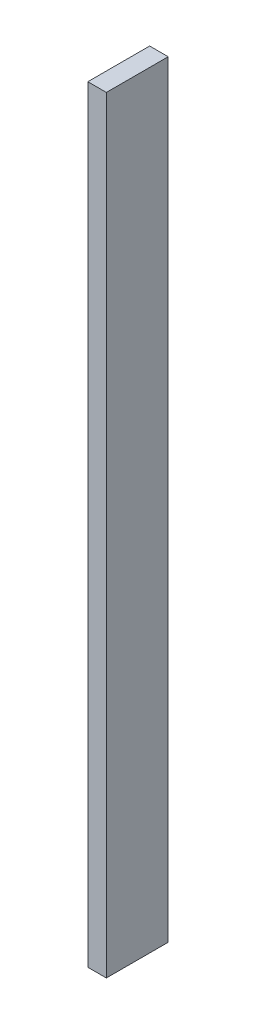
SolidWorks part; units mm, degrees
material "Rubber"
ref_plane "Front Plane" through (0, 0, 0) normal (1, 0, 0) x (0, 1, 0)
ref_plane "Top Plane" through (0, 0, 0) normal (0, 0, 1) x (0, 1, 0)
ref_plane "Right Plane" through (0, 0, 0) normal (0, 1, 0) x (-1, 0, 0)
sketch "Sketch1" plane through (0, 0, 0) normal (0, 0, 1) x (0, 1, 0)
  line L1 (-62, -1.5) -> (62, -1.5)
  line L2 (-62, -1.5) -> (-62, 1.5)
  line L3 (-62, 1.5) -> (62, 1.5)
  line L4 (62, -1.5) -> (62, 1.5)
  line L5 (-62, -1.5) -> (62, 1.5) construction
  line L6 (-62, 1.5) -> (62, -1.5) construction
  point P0 (0, 0)
  dimension "D1" = 3
  dimension "D2" = 124
extrude "Boss-Extrude1" add sketch "Sketch1" along normal blind 10
